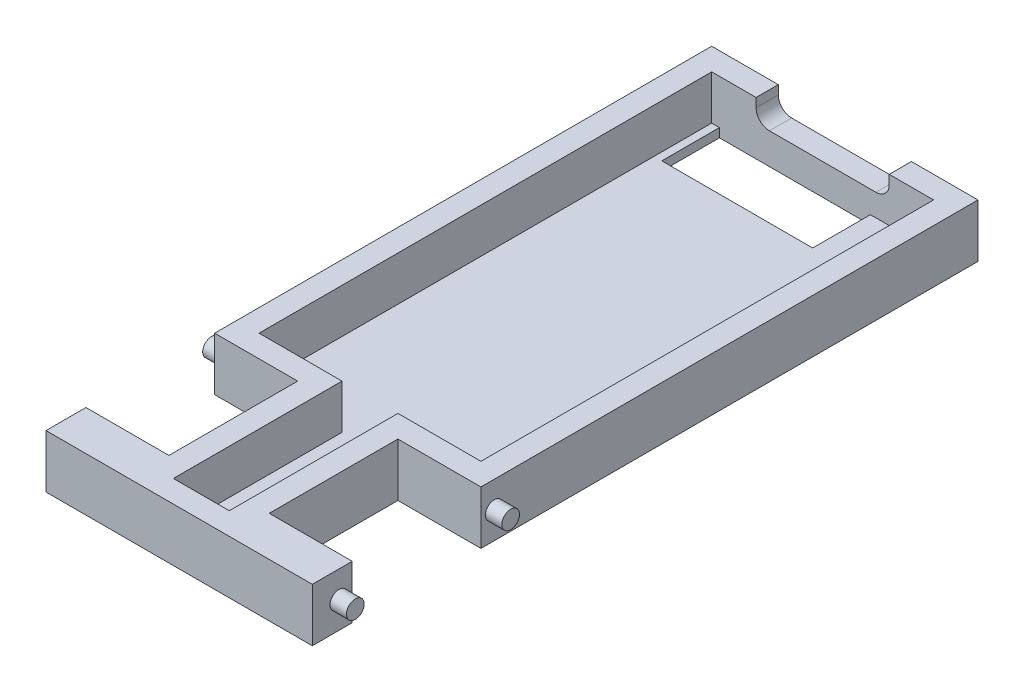
SolidWorks part; units mm, degrees
ref_plane "Front Plane" through (0, 0, 0) normal (0, 0, 1) x (1, 0, 0)
ref_plane "Top Plane" through (0, 0, 0) normal (0, 1, 0) x (1, 0, 0)
ref_plane "Right Plane" through (0, 0, 0) normal (1, 0, 0) x (0, 0, -1)
sketch "Sketch1" plane through (0, 0, 0) normal (0, 1, 0) x (1, 0, 0)
  line L1 (0, 0) -> (60, 0)
  line L2 (0, 0) -> (0, -150)
  line L3 (0, -150) -> (60, -150)
  line L4 (60, 0) -> (60, -150)
  line L5 (5, -5) -> (55, -5)
  line L6 (5, -5) -> (5, -145)
  line L7 (5, -145) -> (55, -145)
  line L8 (55, -5) -> (55, -145)
  line L9 (36.25, -45.8678) -> (23.75, -45.8678)
  line L10 (36.25, -45.8678) -> (36.25, -23.3678)
  line L11 (36.25, -23.3678) -> (23.75, -23.3678)
  line L12 (23.75, -45.8678) -> (23.75, -23.3678)
  point P9 (30, -5)
  point P10 (30, 0)
  point P11 (5, -75)
  point P12 (0, -75)
  point P17 (30, -23.3678)
  dimension "D1" = 60
  dimension "D2" = 150
  dimension "D3" = 5
  dimension "D4" = 5
  dimension "D5" = 22.5
  dimension "D6" = 12.5
extrude "Boss-Extrude1" add sketch "Sketch1" along normal blind 10 contours L4 L1 L2 L3 L5 L8 L7 L6 region at (30, 0, 1.6155)
extrude "Boss-Extrude2" add sketch "Sketch1<2>" against normal blind 2 contours L8 L5 L6 L7 | L4 L1 L2 L3 L5 L8 L7 L6 | L12 L9 L10 L11 region at (30, 0, 1.6155) region at (30, 0, 76.6904) region at (30, 0, 34.6178)
sketch "Sketch1<2>" plane through (0, 0, 0) normal (0, 1, 0) x (1, 0, 0) same geometry as "Sketch1"
sketch "Sketch2" plane through (0, 0, 0) normal (-1, 0, 0) x (0, 0, 1)
  line L1 (144, 4) -> (109, 4) construction
  line L2 (150, 10) -> (150, -2) construction
  line L4 (141, -2) -> (112, -2)
  line L5 (141, -2) -> (141, 10)
  line L6 (141, 10) -> (112, 10)
  line L7 (112, -2) -> (112, 10)
  line L8 (0, -2) -> (150, -2) construction
  line L9 (0, 10) -> (150, 10) construction
  circle A2 centre (144, 4) radius 2
  circle A3 centre (109, 4) radius 2
  circle A4 centre (126.5, 4) radius 14.5 construction
  point P11 (150, 4)
  dimension "D1" = 29
  dimension "D2" = 4
  dimension "D3" = 35
  dimension "D4" = 6
extrude "Cut-Extrude1" cut sketch "Sketch2" against normal blind 18.7 contours L5 L4 L7 L6
extrude "Boss-Extrude3" add sketch "Sketch2<3>" along normal blind 3.7 contours A3 | A2 region at (0, 4, 144) region at (0, 4, 109)
sketch "Sketch2<3>" plane through (0, 0, 0) normal (-1, 0, 0) x (0, 0, 1) same geometry as "Sketch2"
ref_plane "Plane1" through (30, 0, 0) normal (-1, 0, 0) x (0, 0, 1)
mirror "Mirror1" about plane through (30, 0, 0) normal (-1, 0, 0) of "Boss-Extrude3", "Cut-Extrude1"
sketch "Sketch3" plane through (0, 0, 0) normal (0, 1, 0) x (1, 0, 0)
  line L0 (0, -107) -> (23.7, -107)
  line L1 (23.7, -107) -> (23.7, -146)
  line L2 (23.7, -146) -> (0, -146)
  line L3 (60, -146) -> (36.3, -146)
  line L4 (36.3, -146) -> (36.3, -107)
  line L5 (36.3, -107) -> (60, -107)
  line L12 (60, -112) -> (60, 0)
  line L17 (0, -150) -> (60, -150)
  line L18 (0, -141) -> (0, -150)
  line L19 (18.7, -141) -> (0, -141)
  line L20 (18.7, -112) -> (18.7, -141)
  line L21 (0, -112) -> (18.7, -112)
  line L22 (0, 0) -> (0, -112)
  line L23 (60, 0) -> (0, 0)
  line L24 (60, -112) -> (60, 0)
  line L29 (0, -150) -> (60, -150)
  line L30 (0, -141) -> (0, -150)
  line L31 (18.7, -141) -> (0, -141)
  line L32 (18.7, -112) -> (18.7, -141)
  line L33 (0, -112) -> (18.7, -112)
  line L34 (0, 0) -> (0, -112)
  line L35 (60, 0) -> (0, 0)
  line L38 (41.3, -112) -> (60, -112)
  line L39 (41.3, -112) -> (60, -112)
  line L40 (41.3, -141) -> (41.3, -112)
  line L41 (41.3, -141) -> (41.3, -112)
  line L42 (60, -141) -> (41.3, -141)
  line L43 (60, -141) -> (41.3, -141)
  line L44 (60, -150) -> (60, -141)
  line L45 (60, -150) -> (60, -141)
  point P1 (58.1954, -93.5119)
  line M13 (41.3, -112) -> (55, -112)
  line M14 (55, -112) -> (55, -5)
  line M16 (5, -5) -> (5, -112)
  line M17 (5, -112) -> (18.7, -112)
  line M18 (18.7, -112) -> (18.7, -141)
  line M19 (18.7, -141) -> (5, -141)
  line M20 (5, -141) -> (5, -145)
  line M21 (5, -145) -> (55, -145)
  line M22 (55, -145) -> (55, -141)
  line M23 (55, -141) -> (41.3, -141)
  line M24 (41.3, -141) -> (41.3, -112)
  dimension "D1" = 0
  dimension "D2" = 5
  dimension "D3" = 5
extrude "Boss-Extrude4" add sketch "Sketch3" along normal up to surface (10 mm away) contours L1 L0 M16 M17 M18 M19 M20 M21 | M21 M22 M23 M24 M13 M14 region at (14.35, 0, 107.4235) region at (36.7235, 0, 126) up to face at (30, 10, 57.25)
sketch "Sketch4" plane through (0, -2, 0) normal (0, -1, 0) x (1, 0, 0)
  line L1 (6.75, 5) -> (40.75, 5)
  line L2 (6.75, 5) -> (6.75, 18)
  line L3 (6.75, 18) -> (40.75, 18)
  line L4 (40.75, 5) -> (40.75, 18)
  line L5 (30, 6.6) -> (30, -6.6) construction
  line L6 (5, 5) -> (55, 5) construction
  point P6 (72.2692, 17.5705)
  point P9 (0, 0)
  dimension "D1" = 34
  dimension "D2" = 10.75
  dimension "D3" = 13
extrude "Cut-Extrude2" cut sketch "Sketch4" against normal through all both and the other way through all
sketch "Sketch5" plane through (0, 0, 0) normal (0, 0, -1) x (-1, 0, 0)
  line L0 (0, 10) -> (-60, 10) construction
  line L1 (-45, 10) -> (-15, 10)
  line L2 (-45, 10) -> (-45, 5)
  line L3 (-45, 5) -> (-15, 5)
  line L4 (-15, 10) -> (-15, 5)
  line L6 (-30, -6.6) -> (-30, 6.6) construction
  point P6 (-30, 10)
  dimension "D1" = 5
  dimension "D2" = 30
extrude "Cut-Extrude3" cut sketch "Sketch5" against normal up to next
fillet "Fillet1" radius 3 2 edges at (15, 5, 2.5) (45, 5, 2.5)
